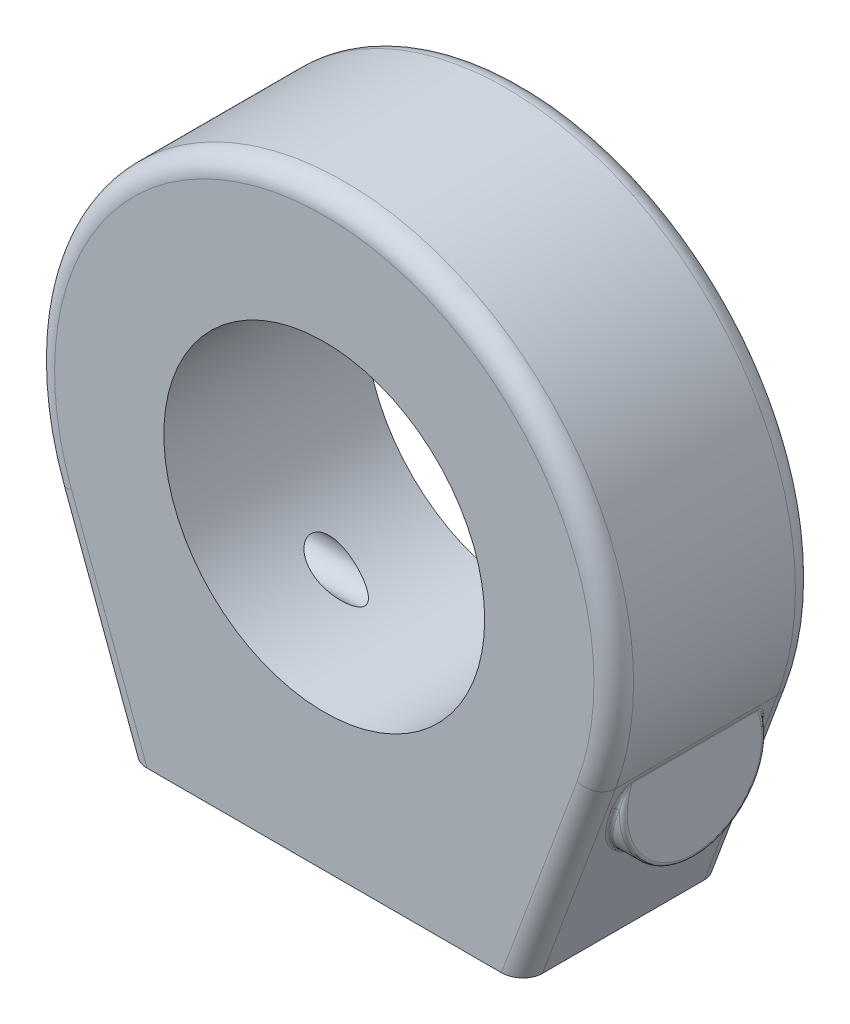
SolidWorks part; units mm, degrees
ref_plane "Front Plane" through (0, 0, 0) normal (0, 0, 1) x (1, 0, 0)
ref_plane "Top Plane" through (0, 0, 0) normal (0, 1, 0) x (1, 0, 0)
ref_plane "Right Plane" through (0, 0, 0) normal (1, 0, 0) x (0, 0, -1)
sketch "Sketch1" plane through (0, 0, 0) normal (0, 0, 1) x (1, 0, 0)
  line L0 (-50, -75) -> (50, -75)
  line L1 (0, 0) -> (0, -75) construction
  line L2 (50, -75) -> (68.425, -25.4367)
  line L3 (-50, -75) -> (-68.425, -25.4367)
  circle A0 centre (0, 0) radius 73
  circle A1 centre (0, 0) radius 40.45
  point P6 (0, -75)
  dimension "D1" = 146
  dimension "D4" = 80.9
  dimension "D2" = 100
  dimension "D3" = 75
extrude "Boss-Extrude1" add sketch "Sketch1" along normal blind 50.8 contours A0 | L1 A0 L3 L0 | A0 L1 L0 L2 region at (-40.4059, -64.8267, 0) region at (40.4059, -64.8267, 0) region at (-12.5569, 69.815, 0)
fillet "Fillet1" radius 5 6 edges at (59.2125, -50.2183, 50.8) (-59.2125, -50.2183, 50.8) (59.2125, -50.2183, 0) (-59.2125, -50.2183, 0) (0, 73, 50.8) (0, 73, 0)
ref_plane "Plane1" through (-68, 0, 0) normal (1, 0, 0) x (0, 0, -1)
sketch "Sketch2" plane through (-68, 0, 0) normal (1, 0, 0) x (0, 0, -1)
  circle A0 centre (-25.4, -33) radius 18
  dimension "D2" = 36
  dimension "D1" = 33
  dimension "D3" = 25.4
extrude "Boss-Extrude2" add sketch "Sketch2" along normal up to next
fillet "Fillet2" radius 1 3 edges at (-58.9219, -51, 25.4) (-68, -26.5798, 25.4) (-68, -51, 25.4)
mirror "Mirror2" about plane through (0, 0, 0) normal (1, 0, 0) of "Fillet2", "Boss-Extrude2"
sketch "Sketch3" plane through (-68, 0, 0) normal (-1, 0, 0) x (0, 0, 1)
  circle A1 centre (25.4, -33) radius 10.5
  dimension "D1" = 21
extrude "Cut-Extrude1" cut sketch "Sketch3" against normal blind 14
sketch "Sketch4" plane through (-54, 0, 0) normal (-1, 0, 0) x (0, 0, 1)
  circle A0 centre (25.4, -33) radius 4.5
  dimension "D1" = 9
extrude "Cut-Extrude2" cut sketch "Sketch4" against normal up to next
